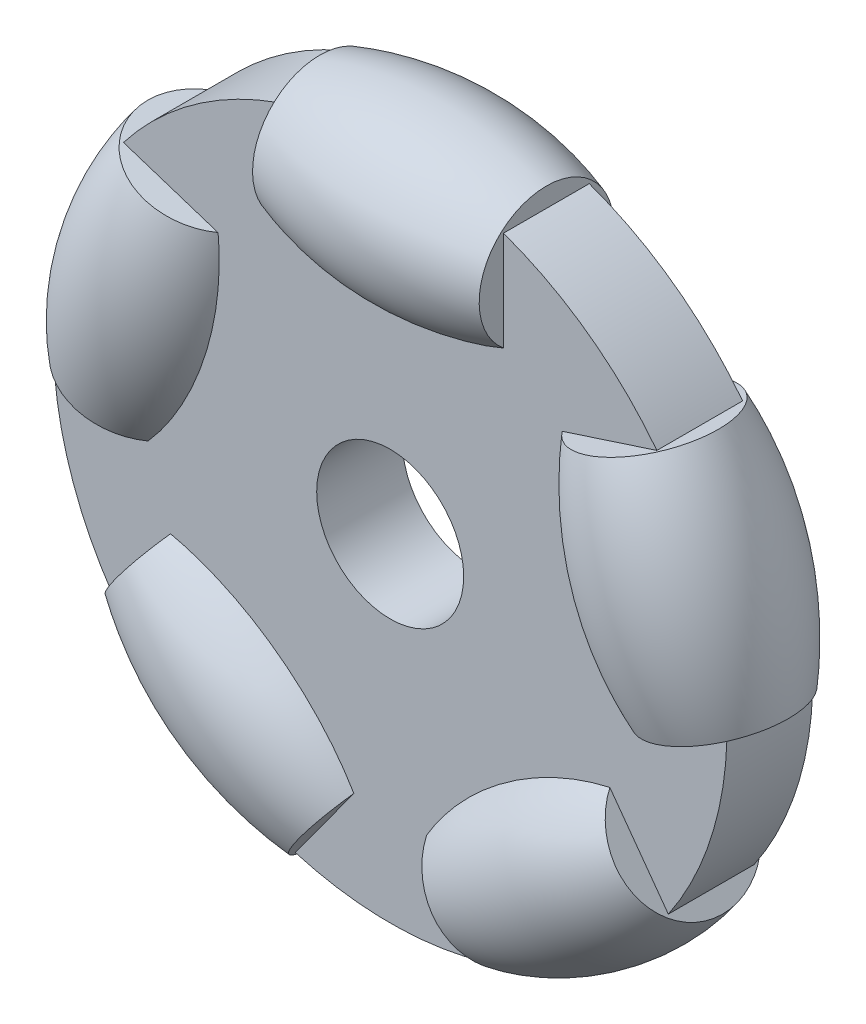
SolidWorks part; units mm, degrees
ref_plane "Front Plane" through (0, 0, 0) normal (0, 0, 1) x (1, 0, 0)
ref_plane "Top Plane" through (0, 0, 0) normal (0, 1, 0) x (1, 0, 0)
ref_plane "Right Plane" through (0, 0, 0) normal (1, 0, 0) x (0, 0, -1)
sketch "Sketch1" plane through (0, 0, 0) normal (0, 0, 1) x (1, 0, 0)
  line L0 (23.7817, -1.9989) -> (28.9984, -0.3039)
  line L6 (-9.25, 22) -> (-9.25, 27.4852)
  line L8 (9.25, 22) -> (9.25, 27.4852)
  line L9 (18.0648, 15.5956) -> (23.7817, -1.9989)
  line L10 (18.0648, 15.5956) -> (23.2816, 17.2907)
  line L11 (-9.25, 22) -> (9.25, 22)
  line L12 (5.4479, -23.2354) -> (8.672, -27.673)
  line L13 (20.4147, -12.3614) -> (5.4479, -23.2354)
  line L14 (20.4147, -12.3614) -> (23.6388, -16.799)
  line L15 (-20.4147, -12.3614) -> (-23.6388, -16.799)
  line L16 (-5.4479, -23.2354) -> (-20.4147, -12.3614)
  line L17 (-5.4479, -23.2354) -> (-8.672, -27.673)
  line L18 (-18.0648, 15.5956) -> (-23.2816, 17.2907)
  line L19 (-23.7817, -1.9989) -> (-18.0648, 15.5956)
  line L20 (-23.7817, -1.9989) -> (-28.9984, -0.3039)
  circle A2 centre (0, 0) radius 29 construction
  arc A3 (-9.25, 27.4852) -> (9.25, 27.4852) centre (0, 0) cw
  circle A4 centre (0, 0) radius 29 construction
  arc A5 (23.2816, 17.2907) -> (28.9984, -0.3039) centre (0, 0) cw
  circle A6 centre (0, 0) radius 29 construction
  arc A7 (23.6388, -16.799) -> (8.672, -27.673) centre (0, 0) cw
  circle A8 centre (0, 0) radius 29 construction
  arc A9 (-8.672, -27.673) -> (-23.6388, -16.799) centre (0, 0) cw
  circle A10 centre (0, 0) radius 29 construction
  arc A11 (-28.9984, -0.3039) -> (-23.2816, 17.2907) centre (0, 0) cw
  circle A12 centre (0, 0) radius 27.5
  point P1 (0, 16.5148)
  point P31 (0, 0)
  dimension "D1" = 58
  dimension "D2" = 5
  dimension "D3" = 0
  dimension "D4" = 55
revolve "Revolve16" add sketch "Sketch1" angle 360 about L11
revolve "Revolve17" add sketch "Sketch1<3>" angle 360 about L19
sketch "Sketch1<3>" plane through (0, 0, 0) normal (0, 0, 1) x (1, 0, 0) same geometry as "Sketch1"
revolve "Revolve18" add sketch "Sketch1<4>" angle 360 about L16
sketch "Sketch1<4>" plane through (0, 0, 0) normal (0, 0, 1) x (1, 0, 0) same geometry as "Sketch1"
revolve "Revolve19" add sketch "Sketch1<5>" angle 360 about L13
sketch "Sketch1<5>" plane through (0, 0, 0) normal (0, 0, 1) x (1, 0, 0) same geometry as "Sketch1"
revolve "Revolve20" add sketch "Sketch1<6>" angle 360 about L9
sketch "Sketch1<6>" plane through (0, 0, 0) normal (0, 0, 1) x (1, 0, 0) same geometry as "Sketch1"
extrude "Boss-Extrude1" add sketch "Sketch1<7>" along normal mid plane 7 contours A12
sketch "Sketch1<7>" plane through (0, 0, 0) normal (0, 0, 1) x (1, 0, 0) same geometry as "Sketch1"
sketch "Sketch4" plane through (0, 0, -3.5) normal (0, 0, -1) x (-1, 0, 0)
  circle A0 centre (0, 0) radius 6
  dimension "D1" = 12
extrude "Cut-Extrude8" cut sketch "Sketch4" against normal up to next
ref_plane "Plane1" through (0, 0, 90.5498) normal (0, 0, 1) x (1, 0, 0)
sketch "Sketch12" plane through (0, 0, 90.5498) normal (0, 0, 1) x (1, 0, 0)
  line L0 (23.7817, -1.9989) -> (28.9984, -0.3039)
  line L6 (-9.25, 22) -> (-9.25, 27.4852)
  line L8 (9.25, 22) -> (9.25, 27.4852)
  line L9 (18.0648, 15.5956) -> (23.7817, -1.9989)
  line L10 (18.0648, 15.5956) -> (23.2816, 17.2907)
  line L11 (-9.25, 22) -> (9.25, 22)
  line L12 (5.4479, -23.2354) -> (8.672, -27.673)
  line L13 (20.4147, -12.3614) -> (5.4479, -23.2354)
  line L14 (20.4147, -12.3614) -> (23.6388, -16.799)
  line L15 (-20.4147, -12.3614) -> (-23.6388, -16.799)
  line L16 (-5.4479, -23.2354) -> (-20.4147, -12.3614)
  line L17 (-5.4479, -23.2354) -> (-8.672, -27.673)
  line L18 (-18.0648, 15.5956) -> (-23.2816, 17.2907)
  line L19 (-23.7817, -1.9989) -> (-18.0648, 15.5956)
  line L20 (-23.7817, -1.9989) -> (-28.9984, -0.3039)
  circle A2 centre (0, 0) radius 29 construction
  arc A3 (-9.25, 27.4852) -> (9.25, 27.4852) centre (0, 0) cw
  circle A4 centre (0, 0) radius 29 construction
  arc A5 (23.2816, 17.2907) -> (28.9984, -0.3039) centre (0, 0) cw
  circle A6 centre (0, 0) radius 29 construction
  arc A7 (23.6388, -16.799) -> (8.672, -27.673) centre (0, 0) cw
  circle A8 centre (0, 0) radius 29 construction
  arc A9 (-8.672, -27.673) -> (-23.6388, -16.799) centre (0, 0) cw
  circle A10 centre (0, 0) radius 29 construction
  arc A11 (-28.9984, -0.3039) -> (-23.2816, 17.2907) centre (0, 0) cw
  circle A12 centre (0, 0) radius 27.5
  point P1 (0, 16.5148)
  point P31 (0, 0)
  dimension "D1" = 58
  dimension "D2" = 5
  dimension "D3" = 0
  dimension "D4" = 55
sketch "Sketch13" plane through (0, 0, 90.5498) normal (0, 0, 1) x (1, 0, 0)
  line L0 (0, 29) -> (0, 0)
  arc A0 (9.25, 27.4852) -> (-9.25, 27.4852) centre (0, 0) ccw construction
